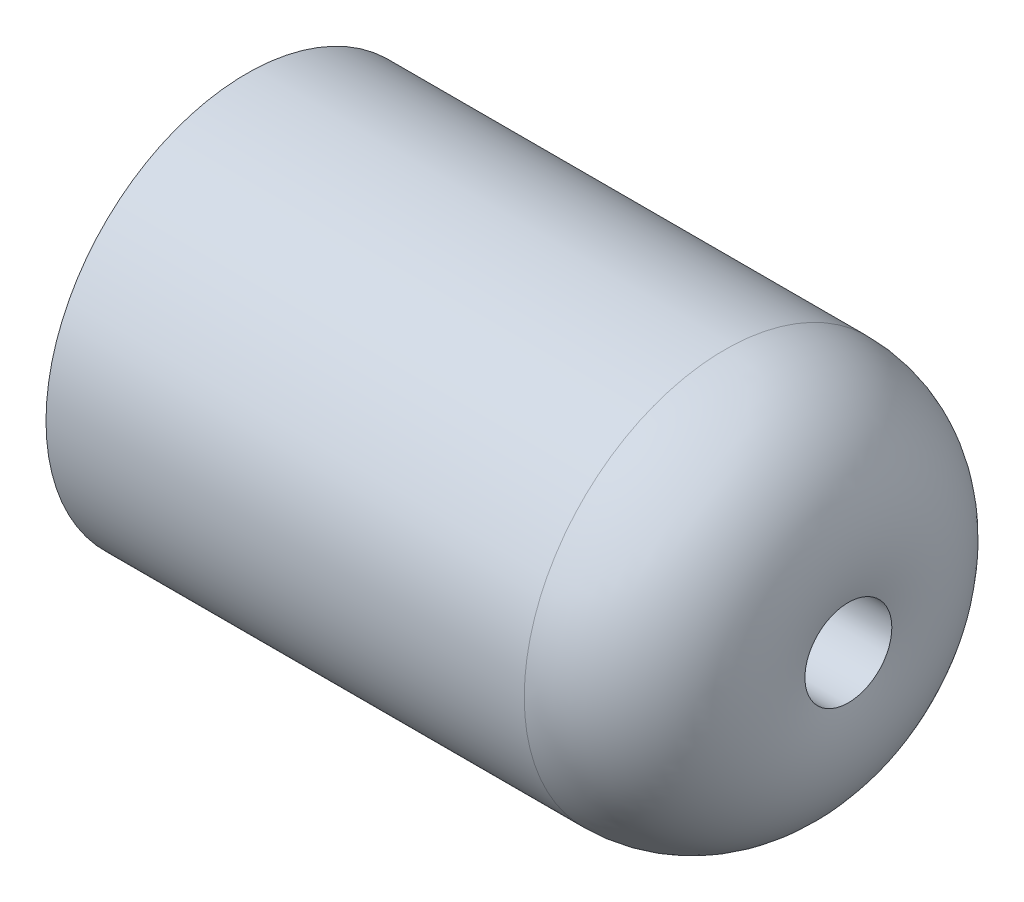
SolidWorks part; units mm, degrees
material "1060 Alloy"
ref_plane "Front Plane" through (0, 0, 0) normal (0, 0, 1) x (1, 0, 0)
ref_plane "Top Plane" through (0, 0, 0) normal (0, 1, 0) x (1, 0, 0)
ref_plane "Right Plane" through (0, 0, 0) normal (1, 0, 0) x (0, 0, -1)
ref_axis "X-axis" through (-88.99, 0, 0) along (1, 0, 0)
ref_axis "Y-axis" through (0, 55, 0) along (0, -1, 0)
ref_axis "Z-axis" through (0, 0, -88.99) along (0, 0, 1)
sketch "Sketch1" plane through (0, 0, 0) normal (0, 0, 1) x (1, 0, 0)
  line L0 (0, 0) -> (-98.0632, 0) construction
  line L2 (0, 0.8255) -> (11.43, 0.8255)
  line L3 (0, 3.81) -> (0, 0.8255)
  line L4 (0, 3.81) -> (9.0839, 3.81)
  arc A1 (9.0839, 3.81) -> (11.43, 0.8255) centre (9.0839, 1.3956) cw
  dimension "D1" = 1.651
  dimension "D2" = 7.62
  dimension "D3" = 11.43
revolve "Revolve1" add sketch "Sketch1" angle 360 about L0
